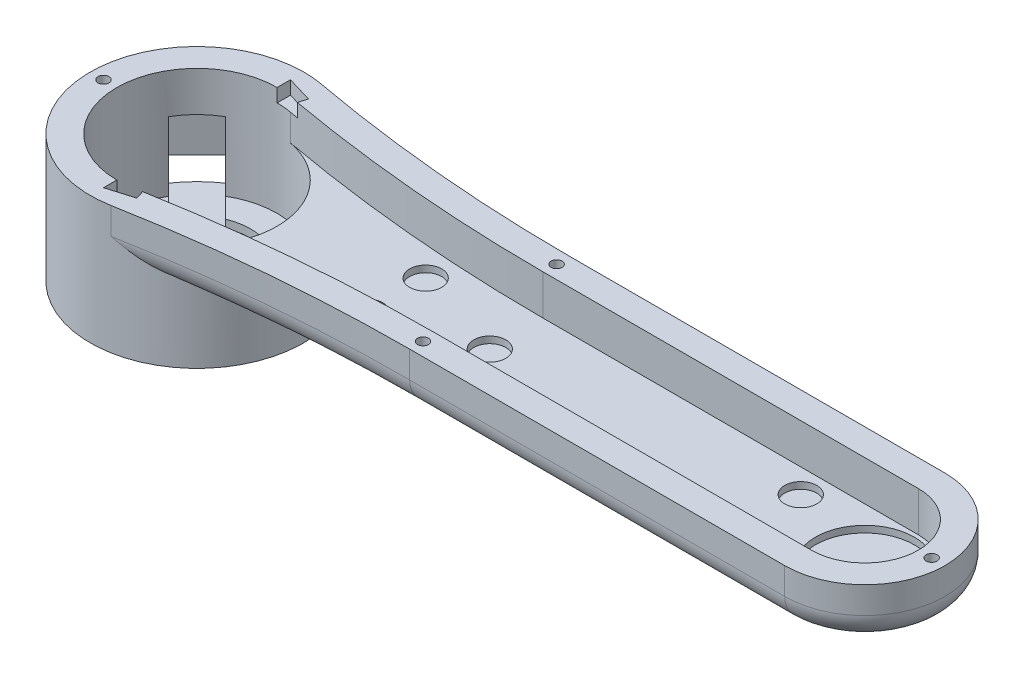
SolidWorks part; units mm, degrees
ref_plane "Front Plane" through (0, 0, 0) normal (0, 0, 1) x (1, 0, 0)
ref_plane "Top Plane" through (0, 0, 0) normal (0, 1, 0) x (1, 0, 0)
ref_plane "Right Plane" through (0, 0, 0) normal (1, 0, 0) x (0, 0, -1)
sketch "Sketch1" plane through (0, 0, 0) normal (0, 1, 0) x (1, 0, 0)
  line L0 (0, 0) -> (250, 0) construction
  line L1 (109.6, 30) -> (109.6, -30) construction
  line L2 (250, 30) -> (109.6, 30)
  line L3 (250, -30) -> (109.6, -30)
  line L4 (109.6, 20) -> (109.6, -20) construction
  line L5 (250, 20) -> (109.6, 20)
  line L6 (250, -20) -> (109.6, -20)
  circle A0 centre (0, 0) radius 30
  circle A1 centre (0, 0) radius 40
  circle A2 centre (109.6, 0) radius 30 construction
  circle A3 centre (250, 0) radius 30
  arc A4 (109.6, 30) -> (7.239, 39.3395) centre (109.6, 595.608) cw
  arc A5 (109.6, -30) -> (7.239, -39.3395) centre (109.6, -595.608) ccw
  circle A6 centre (109.6, 0) radius 20 construction
  circle A7 centre (250, 0) radius 20
  arc A8 (109.6, 20) -> (5.4293, 29.5046) centre (109.6, 595.608) cw
  arc A9 (109.6, -20) -> (5.4293, -29.5046) centre (109.6, -595.608) ccw
  dimension "D1" = 60
  dimension "D2" = 80
  dimension "D4" = 140.4
  dimension "D5" = 60
  dimension "D7" = 40
  dimension "D3" = 250
  dimension "D6" = 109.6
extrude "Boss-Extrude1" add sketch "Sketch1" along normal blind 15 contours A1 A9 A0 A8 | A8 L5 A3 L2 A4 A1 | L6 A9 A1 A5 L3 A3 | A7 L6 A3 L5 region at (128.9716, 0, -26.0392) region at (270.6501, 0, -20.6501) region at (19.7576, 0, -33.545) region at (128.9716, 0, 26.0392)
sketch "Sketch2" plane through (0, 0, 0) normal (0, -1, 0) x (1, 0, 0)
  circle A0 centre (0, 0) radius 40
  circle A1 centre (0, 0) radius 30
  arc A2 (7.239, 39.3395) -> (7.239, -39.3395) centre (0, 0) ccw construction
  arc A3 (5.4293, 29.5046) -> (5.4293, -29.5046) centre (0, 0) ccw construction
extrude "Boss-Extrude2" add sketch "Sketch2" along normal blind 25.8
sketch "Sketch3" plane through (0, -25.8, 0) normal (0, -1, 0) x (1, 0, 0)
  circle A0 centre (0, 0) radius 40 construction
  circle A1 centre (0, 0) radius 40
extrude "Boss-Extrude3" add sketch "Sketch3" along normal blind 7
sketch "Sketch4" plane through (0, 0, 0) normal (0, -1, 0) x (1, 0, 0)
  line L0 (250, 30) -> (109.6, 30) construction
  line L1 (250, -30) -> (109.6, -30) construction
  line L2 (250, 30) -> (109.6, 30)
  line L3 (250, -30) -> (109.6, -30)
  circle A0 centre (0, 0) radius 40 construction
  arc A1 (7.239, 39.3395) -> (109.6, 30) centre (109.6, 595.608) ccw construction
  circle A2 centre (250, 0) radius 30 construction
  arc A3 (109.6, -30) -> (7.239, -39.3395) centre (109.6, -595.608) ccw construction
  circle A4 centre (0, 0) radius 40
  arc A5 (7.239, 39.3395) -> (109.6, 30) centre (109.6, 595.608) ccw
  circle A6 centre (250, 0) radius 30
  arc A7 (109.6, -30) -> (7.239, -39.3395) centre (109.6, -595.608) ccw
  circle A8 centre (109.6, 0) radius 6
  circle A9 centre (250, 0) radius 18.5
  arc M1 (30.8954, -25.4061) -> (7.239, -39.3395) centre (0, 0) cw
  arc M2 (7.239, -39.3395) -> (109.6, -30) centre (109.6, -595.608) cw
  line M3 (109.6, -30) -> (250, -30)
  arc M4 (250, -30) -> (250, 30) centre (250, 0) ccw
  line M5 (250, 30) -> (109.6, 30)
  arc M6 (109.6, 30) -> (7.239, 39.3395) centre (109.6, 595.608) cw
  arc M7 (7.239, 39.3395) -> (30.8954, 25.4061) centre (0, 0) cw
  arc M8 (30.8954, 25.4061) -> (109.6, 20) centre (109.6, 595.608) ccw
  line M9 (109.6, 20) -> (250, 20)
  arc M10 (250, 20) -> (250, -20) centre (250, 0) cw
  line M11 (250, -20) -> (109.6, -20)
  arc M12 (109.6, -20) -> (30.8954, -25.4061) centre (109.6, -595.608) ccw
  dimension "D1" = 12
  dimension "D2" = 37
extrude "Boss-Extrude4" add sketch "Sketch4" along normal blind 5 contours A6 A4 A8 M9 M8 M12 M11 | A6 A9 M9 M11 M10 | A6 M4 M9 M10 M11 | A6 M5 M6 M7 M8 M9 | A6 M11 M12 M1 M2 M3 region at (128.9716, 0, 26.0392) region at (270.6501, 0, 20.6501) region at (238.8197, 0, 19.3597) region at (127.9252, 0, 0) region at (128.9716, 0, -26.0392)
sketch "Sketch6" plane through (0, -5, 0) normal (0, -1, 0) x (1, 0, 0)
  circle A0 centre (109.6, 0) radius 6 construction
  circle A1 centre (109.6, 0) radius 6
  circle A2 centre (250, 0) radius 18.5 construction
  circle A3 centre (250, 0) radius 18.5
extrude "Boss-Extrude5" add sketch "Sketch6" against normal blind 2.5
sketch "Sketch7" plane through (0, 15, 0) normal (0, 1, 0) x (1, 0, 0)
  line L0 (0, -30) -> (0, -35)
  line L1 (0, -35) -> (9.5831, -32.1429)
  line L2 (0, -31.305) -> (8.5714, -28.7494) construction
  line L3 (9.5831, -32.1429) -> (8.5714, -28.7494)
  line L4 (0, 0) -> (-18.861, 0) construction
  line L5 (0, 31.305) -> (8.5714, 28.7494) construction
  line L6 (9.5831, 32.1429) -> (8.5714, 28.7494)
  line L7 (0, 35) -> (9.5831, 32.1429)
  line L8 (0, 30) -> (0, 35)
  circle A0 centre (0, 0) radius 30 construction
  circle A1 centre (0, 0) radius 30 construction
  arc A2 (0, -30) -> (8.5595, -28.753) centre (0, 0) ccw
  arc A3 (0, 30) -> (8.5595, 28.753) centre (0, 0) cw
  arc M14 (109.6, -20) -> (5.4293, -29.5046) centre (109.6, -595.608) ccw
  arc M15 (5.4293, -29.5046) -> (5.4293, 29.5046) centre (0, 0) cw
  arc M16 (5.4293, 29.5046) -> (109.6, 20) centre (109.6, 595.608) ccw
  dimension "D1" = 5
  dimension "D2" = 10
extrude "Cut-Extrude1" cut sketch "Sketch7" against normal blind 5 contours L1 L3 L0 M14 M15 | L8 L6 L7 M15 M16 region at (4.2835, 15, 31.6882) region at (4.2835, 15, -31.6882)
fillet "Fillet1" radius 10 5 edges at (58.2069, -5, -32.3397) (179.8, -5, -30) (280, -5, 0) (58.2069, -5, 32.3397) (179.8, -5, 30)
sketch "Sketch8" plane through (0, -32.8, 0) normal (0, -1, 0) x (1, 0, 0)
  circle A0 centre (0, 0) radius 15 construction
  circle A1 centre (0, 15) radius 1.5
  circle A2 centre (15, 0) radius 1.5
  circle A3 centre (0, -15) radius 1.5
  circle A4 centre (-15, 0) radius 1.5
  point P14 (0, 0)
  dimension "D1" = 30
  dimension "D2" = 3
  dimension "D3" = 4
extrude "Cut-Extrude2" cut sketch "Sketch8" against normal through all both and the other way through all
sketch "Sketch13" plane through (0, -32.8, 0) normal (0, -1, 0) x (-1, 0, 0)
  circle A0 centre (0, -15) radius 3.5
  circle A4 centre (-15, 0) radius 3.5
  circle A5 centre (0, 15) radius 3.5
  circle A6 centre (15, 0) radius 3.5
  point P15 (0, 0)
  dimension "D1" = 7
  dimension "D2" = 4
extrude "Cut-Extrude4" cut sketch "Sketch13" against normal blind 2
sketch "Sketch9" plane through (0, -32.8, 0) normal (0, -1, 0) x (1, 0, 0)
  circle A0 centre (0, 0) radius 30 construction
  circle A1 centre (0, 30) radius 2.05
  circle A2 centre (30, 0) radius 2.05
  circle A3 centre (0, -30) radius 2.05
  circle A4 centre (-30, 0) radius 2.05
  point P14 (0, 0)
  dimension "D1" = 60
  dimension "D2" = 4.1
  dimension "D3" = 4
extrude "Cut-Extrude3" cut sketch "Sketch9" against normal blind 6
sketch "Sketch11" plane through (0, 15, 0) normal (0, 1, 0) x (1, 0, 0)
  line L0 (280, 0) -> (-40, 0) construction
  line L1 (109.6, -30) -> (109.6, 30) construction
  arc A0 (250, -30) -> (250, 30) centre (250, 0) ccw construction
  arc A1 (7.239, 39.3395) -> (7.239, -39.3395) centre (0, 0) ccw construction
hole_wizard "Ø4.0mm Dowel Hole1" positions "3DSketch1" profile "Sketch10" hole size "Ø4.0" standard "GB"
sketch3d "3DSketch1"
  line L0 (250, 15, 30) -> (109.6, 15, 30) construction
  line L2 (250, 15, -20) -> (109.6, 15, -20) construction
  line L3 (280, 15, 0) -> (-40, 15, 0) construction
  line L4 (109.6, 15, 30) -> (109.6, 15, -30) construction
  arc A0 (250, 15, 20) -> (250, 15, -20) centre (250, 15, 0) ccw construction
  arc A3 (0, 15, -30) -> (0, 15, 30) centre (0, 15, 0) ccw construction
  point P0 (275, 15, 0)
  point P2 (-35, 15, 0)
  point P4 (109.6, 15, 25)
  point P6 (109.6, 15, -25)
  point P10 (250, 35, 0)
  point P21 (0, 45, 0)
  dimension "D1" = 25
  dimension "D2" = 35
  dimension "D3" = 5
  dimension "D4" = 5
sketch "Sketch10" plane through (275, 15, 0) normal (1, 0, 0) x (0, 0, 1)
  line L0 (0, 0) -> (0, 8.2318)
  line L1 (0, 8.2318) -> (2.05, 7)
  line L2 (2.05, 7) -> (2.05, 0)
  line L5 (2.05, 0) -> (0, 0)
  line L10 (0, 8.2318) -> (-2.05, 7) construction
  line L11 (0, -6.35) -> (0, 107.95) construction
  dimension "Hole Dia." = 4.1
  dimension "Hole Depth" = 7
  dimension "Drill Angle" = 118
sketch "Sketch14" plane through (0, 0, 0) normal (0, 1, 0) x (1, 0, 0)
  line L0 (70.249, 0) -> (220.1457, 0) construction
  circle A0 centre (74.6, -11) radius 6
  circle A1 centre (74.6, 11) radius 6
  circle A2 centre (215, -11) radius 6
  circle A3 centre (215, 11) radius 6
  circle A4 centre (109.6, 0) radius 6 construction
  circle A5 centre (250, 0) radius 18.5 construction
  dimension "D1" = 35
  dimension "D2" = 35
  dimension "D3" = 22
  dimension "D4" = 11
extrude "Cut-Extrude5" cut sketch "Sketch14" against normal blind 2.5
sketch "Sketch15" plane through (0, 0, 0) normal (0, 1, 0) x (1, 0, 0)
  line L0 (-7.4246, 18.0312) -> (-18.0312, 7.4246)
  line L1 (-7.4246, 18.0312) -> (-20.1525, 30.7591)
  line L2 (-18.0312, 7.4246) -> (-30.7591, 20.1525)
  line L3 (-20.1525, 30.7591) -> (-30.7591, 20.1525)
  line L4 (0, 0) -> (-32.928, 32.928) construction
  line L5 (0, 0) -> (-55.1294, 0) construction
  point P3 (-25.4558, 25.4558)
  point P19 (-13.7886, 24.3952)
  dimension "D2" = 36
  dimension "D3" = 15
  dimension "D4" = 18
  dimension "D5" = 45
extrude "Cut-Extrude6" cut sketch "Sketch15" against normal blind 28.8
sketch "Sketch16" plane through (0, -25.8, 0) normal (0, 1, 0) x (1, 0, 0)
  circle A1 centre (0, 0) radius 20
  dimension "D1" = 40
extrude "Cut-Extrude7" cut sketch "Sketch16" against normal blind 3
sketch "Sketch17" plane through (0, -32.8, 0) normal (0, -1, 0) x (1, 0, 0)
  circle A0 centre (0, 0) radius 6
  dimension "D1" = 12
extrude "Cut-Extrude8" cut sketch "Sketch17" against normal up to next
sketch "Sketch18" plane through (-25.4558, 0, -25.4558) normal (0.7071, 0, 0.7071) x (0.7071, 0, -0.7071)
  line L1 (-7.5, -28.8) -> (7.5, -28.8)
  line L2 (-7.5, -28.8) -> (-7.5, -17.3026)
  line L3 (-7.5, -17.3026) -> (7.5, -17.3026)
  line L4 (7.5, 0) -> (-7.5, 0)
  line L5 (-7.5, 0) -> (-7.5, -28.8)
  line L6 (-7.5, -28.8) -> (7.5, -28.8)
  line L7 (7.5, -28.8) -> (7.5, 0)
  line L8 (7.5, 0) -> (-7.5, 0)
  line L9 (-7.5, 0) -> (-7.5, -28.8)
  line L10 (-7.5, -28.8) -> (7.5, -28.8)
  line L11 (7.5, -28.8) -> (7.5, 0)
  line L12 (7.5, -28.8) -> (7.5, -17.3026)
  line M10 (-7.5, 0) -> (-7.5, -28.8)
  line M11 (-7.5, -28.8) -> (7.5, -28.8)
  line M12 (7.5, -28.8) -> (7.5, 0)
  dimension "D1" = 0
extrude "Cut-Extrude9" cut sketch "Sketch18" against normal through all contours L3 M10 M11 M12 region at (-25.4558, -23.0513, -25.4558)
